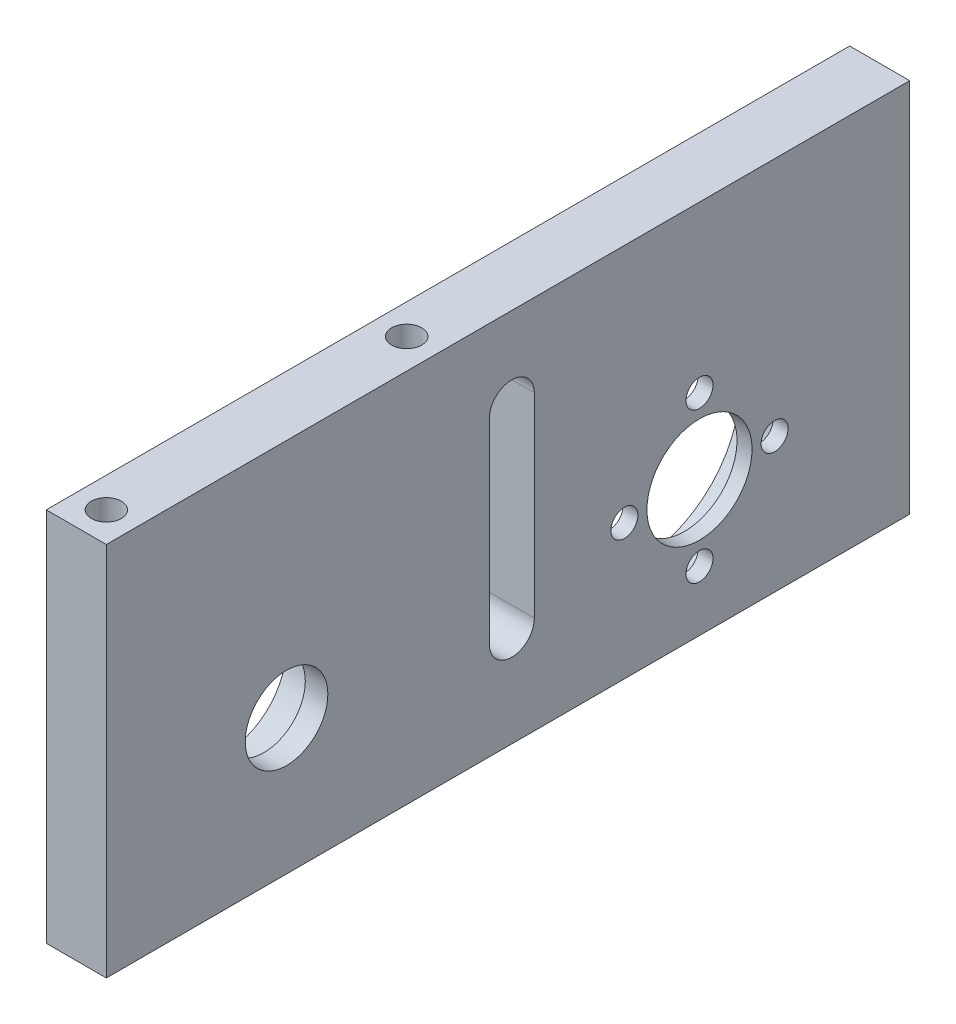
SolidWorks part; units mm, degrees
ref_plane "Plan de face" through (0, 0, 0) normal (0, 0, 1) x (1, 0, 0)
ref_plane "Plan de dessus" through (0, 0, 0) normal (0, 1, 0) x (1, 0, 0)
ref_plane "Plan de droite" through (0, 0, 0) normal (1, 0, 0) x (0, 0, -1)
sketch "Esquisse1" plane through (0, 0, 0) normal (0, 1, 0) x (1, 0, 0)
  line L8 (-11, 113) -> (-19, 113)
  line L17 (-11, 113) -> (-11, 6)
  line L21 (-19, 6) -> (-11, 6)
  line L22 (-19, 6) -> (-19, 113)
extrude "Boss.-Extru.1" add sketch "Esquisse1" along normal blind 50 contours L17 L8 region at (-15, 0, -59.5)
sketch "Esquisse4" plane through (-19, 0, 0) normal (-1, 0, 0) x (0, 0, 1)
  line L1 (-85, 18) -> (-95, 18) construction
  line L2 (-85, 18) -> (-85, 8) construction
  line L4 (-85, 18) -> (-85, 0) construction
  line L5 (-95, 18) -> (-85, 18) construction
  line L6 (-85, 18) -> (-85, 28) construction
  line L7 (-85, 28) -> (-85, 18) construction
  line L8 (-85, 18) -> (-75, 18) construction
  line L9 (-75, 18) -> (-85, 18) construction
  line L10 (-6, 0) -> (-113, 0) construction
  line L11 (-85, 0) -> (-113, 0) construction
  circle A0 centre (-85, 18) radius 13.4
  circle A1 centre (-85, 18) radius 7
  circle A2 centre (-85, 8) radius 1.8
  circle A3 centre (-75, 18) radius 1.8
  circle A4 centre (-85, 28) radius 1.8
  circle A5 centre (-95, 18) radius 1.8
  dimension "D1" = 28
  dimension "D2" = 14
  dimension "D3" = 26.8
  dimension "D4" = 3.6
  dimension "D5" = 10
  dimension "D6" = 10
  dimension "D7" = 10
  dimension "D8" = 10
extrude "Enlèv. mat.-Extru.2" cut sketch "Esquisse4" against normal blind 10 contours A5 | A4 | A2 | A3 region at (-19, 8, -85) region at (-19, 18, -75) region at (-19, 28, -85) region at (-19, 18, -95)
extrude "Enlèv. mat.-Extru.3" cut sketch "Esquisse4<3>" against normal blind 6 contours A0 A5 A4 A3 A2 A1 region at (-19, 18, -98.021)
sketch "Esquisse4<3>" plane through (-19, 0, 0) normal (-1, 0, 0) x (0, 0, 1) same geometry as "Esquisse4"
extrude "Enlèv. mat.-Extru.4" cut sketch "Esquisse4<4>" against normal blind 10 contours A1 region at (-19, 18, -85)
sketch "Esquisse4<4>" plane through (-19, 0, 0) normal (-1, 0, 0) x (0, 0, 1) same geometry as "Esquisse4"
sketch "Esquisse9" plane through (-19, 0, 0) normal (-1, 0, 0) x (0, 0, 1)
  line L0 (-60, 13) -> (-6, 13) construction
  line L1 (-60, 13) -> (-60, 14) construction
  line L2 (-57, 39) -> (-57, 13)
  line L3 (-60, 13) -> (-60, 39) construction
  line L4 (-63, 39) -> (-63, 13)
  line L5 (-6, 50) -> (-6, 0) construction
  circle A11 centre (-60, 39) radius 3
  circle A12 centre (-60, 13) radius 3
  dimension "D1" = 26
  dimension "D2" = 6
  dimension "D4" = 54
extrude "Enlèv. mat.-Extru.5" cut sketch "Esquisse9" against normal blind 10 contours A12 | A12 L2 A11 L4 | A11 region at (-19, 39, -60) region at (-19, 26, -60) region at (-19, 13, -60)
sketch "Esquisse26" plane through (-11, 0, 0) normal (1, 0, 0) x (0, 0, -1)
  line L0 (6, 0) -> (30, 0) construction
  line L2 (113, 0) -> (6, 0) construction
  line L3 (30, 0) -> (30, 18) construction
  circle A0 centre (30, 18) radius 7.95
  dimension "D1" = 15.9
  dimension "D2" = 18
  dimension "D3" = 24
extrude "Enlèv. mat.-Extru.6" cut sketch "Esquisse26" against normal blind 10 contours A0 | A0 region at (-11, 18, -30)
sketch "Esquisse12" plane through (-11, 0, 0) normal (1, 0, 0) x (0, 0, -1)
  circle A0 centre (85, 28) radius 2.7
  circle A1 centre (95, 18) radius 2.7
  circle A2 centre (85, 8) radius 2.7
  circle A3 centre (75, 18) radius 2.7
sketch "Esquisse24" plane through (-11, 0, 0) normal (1, 0, 0) x (0, 0, -1)
  circle A0 centre (30, 18) radius 5.5
  circle A1 centre (30, 18) radius 8.2
extrude "Boss.-Extru.6" add sketch "Esquisse24" against normal blind 3
sketch "Esquisse29" plane through (0, 0, 0) normal (0, -1, 0) x (1, 0, 0)
  line L0 (-19, -6) -> (-19, -14) construction
  line L1 (-11, -6) -> (-11, -54) construction
  line L2 (-11, -113) -> (-11, -6) construction
  line L3 (-11, -54) -> (-19, -54) construction
  line L4 (-19, -6) -> (-19, -113) construction
  line L5 (-19, -54) -> (-19, -46) construction
  line L6 (-19, -14) -> (-11, -6) construction
  line L7 (-19, -46) -> (-11, -54) construction
  line L8 (-11, -54) -> (-19, -54) construction
  line L9 (-19, -113) -> (-11, -113) construction
  line L10 (-11, -113) -> (-11, -105) construction
  line L11 (-11, -105) -> (-19, -105) construction
  line L12 (-19, -105) -> (-19, -113) construction
  line L13 (-19, -113) -> (-11, -105) construction
  line L14 (-11, -105) -> (-19, -105) construction
  line L15 (-19, -105) -> (-11, -113) construction
  line L16 (-19, -54) -> (-11, -46) construction
  line L23 (-19, -6) -> (-11, -14) construction
  line L24 (-11, -113) -> (-11, -6) construction
  circle A0 centre (-15, -109) radius 2
  circle A3 centre (-15, -10) radius 2
  circle A4 centre (-15, -50) radius 2
extrude "Enlèv. mat.-Extru.7" cut sketch "Esquisse29" against normal blind 15
sketch "Esquisse30" plane through (0, 50, 0) normal (0, 1, 0) x (1, 0, 0)
  line L0 (-19, 6) -> (-19, 14) construction
  line L1 (-19, 14) -> (-11, 6) construction
  line L2 (-11, 113) -> (-11, 6) construction
  line L3 (-11, 6) -> (-19, 6) construction
  line L4 (-19, 6) -> (-19, 54) construction
  line L5 (-11, 6) -> (-19, 6) construction
  line L6 (-19, 14) -> (-11, 14) construction
  line L7 (-19, 6) -> (-19, 113) construction
  line L8 (-19, 54) -> (-11, 54) construction
  line L9 (-11, 113) -> (-11, 6) construction
  line L10 (-11, 54) -> (-11, 46) construction
  line L11 (-11, 46) -> (-19, 54) construction
  line L12 (-19, 54) -> (-11, 54) construction
  line L13 (-11, 54) -> (-19, 46) construction
  line L14 (-11, 14) -> (-19, 6) construction
  line L15 (-11, 6) -> (-19, 6) construction
  line L17 (-19, 113) -> (-11, 113) construction
  line L18 (-11, 113) -> (-11, 105) construction
  line L19 (-11, 105) -> (-19, 105) construction
  line L20 (-19, 105) -> (-11, 113) construction
  line L21 (-11, 113) -> (-11, 105) construction
  line L22 (-11, 105) -> (-19, 113) construction
  circle A3 centre (-15, 10) radius 2
  circle A4 centre (-15, 50) radius 2
extrude "Enlèv. mat.-Extru.8" cut sketch "Esquisse30" against normal blind 15
